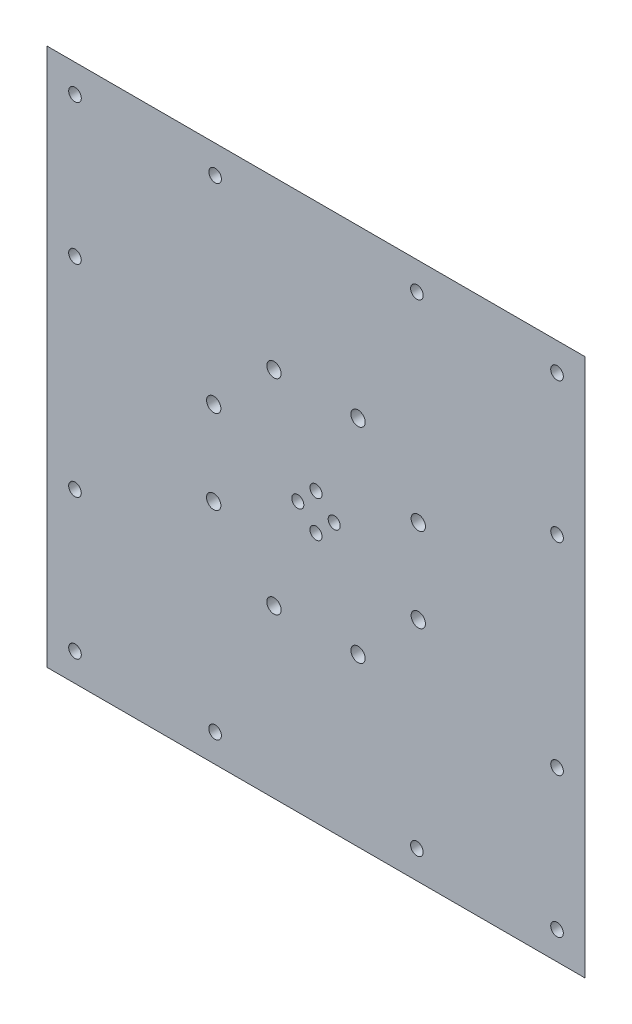
SolidWorks part; units mm, degrees
material "6061 합금"
ref_plane "정면" through (0, 0, 0) normal (0, 0, 1) x (1, 0, 0)
ref_plane "윗면" through (0, 0, 0) normal (0, 1, 0) x (1, 0, 0)
ref_plane "우측면" through (0, 0, 0) normal (1, 0, 0) x (0, 0, -1)
sketch "스케치1" plane through (0, 0, 0) normal (0, 0, 1) x (1, 0, 0)
  line L1 (-100, 100) -> (100, 100)
  line L2 (-100, 100) -> (-100, -100)
  line L3 (-100, -100) -> (100, -100)
  line L4 (100, 100) -> (100, -100)
  line L5 (-100, 100) -> (100, -100) construction
  line L6 (-100, -100) -> (100, 100) construction
  point P0 (0, 0)
  dimension "D1" = 200
  dimension "D2" = 200
extrude "보스-돌출1" add sketch "스케치1" along normal blind 3 contours L1 L4 L3 L2
sketch "스케치5" plane through (0, 0, 3) normal (0, 0, 1) x (1, 0, 0)
  line L1 (-100, 100) -> (100, 100)
  line L2 (-100, 100) -> (-100, -100)
  line L3 (-100, -100) -> (100, -100)
  line L4 (100, 100) -> (100, -100)
extrude "보스-돌출2" add sketch "스케치5" along normal blind 3
sketch "스케치2" plane through (0, 0, 0) normal (0, 0, 1) x (1, 0, 0)
  line L5 (-100, 100) -> (-100, -100) construction
  circle A0 centre (-36.5, 15) radius 2.55
  circle A2 centre (-36.5, -15) radius 2.55
  circle A4 centre (-6.5, 0) radius 2.15
  circle A5 centre (15, 36.5) radius 2.55
  circle A7 centre (-15, 36.5) radius 2.55
  circle A9 centre (0, 6.5) radius 2.15
  circle A10 centre (36.5, -15) radius 2.55
  circle A12 centre (36.5, 15) radius 2.55
  circle A14 centre (6.5, 0) radius 2.15
  circle A15 centre (-15, -36.5) radius 2.55
  circle A17 centre (15, -36.5) radius 2.55
  circle A19 centre (0, -6.5) radius 2.15
  point P2 (-36.5, -15.1647)
  point P46 (0, 0)
  dimension "D1" = 5.1
  dimension "D2" = 93.5
  dimension "D3" = 5.1
  dimension "D4" = 15
  dimension "D5" = 4.3
  dimension "D11" = 30
  dimension "D13" = 30
  dimension "D7" = 0
  dimension "D9" = 30
  dimension "D16" = 4
extrude "컷-돌출1" cut sketch "스케치2" along normal blind 10
chamfer "모따기1" distance 10 angle 45 4 edges at (0, 100, 0) (-100, 0, 0) (0, -100, 0) (100, 0, 0)
sketch "스케치6" plane through (0, 0, 0) normal (0, 0, -1) x (-1, 0, 0)
  line L1 (-96, 96) -> (-86, 96)
  line L2 (-96, 96) -> (-96, 86)
  line L3 (-96, 86) -> (-86, 86)
  line L4 (-86, 96) -> (-86, 86)
  line L5 (-96, -96) -> (-86, -96)
  line L6 (-96, -96) -> (-96, -86)
  line L7 (-96, -86) -> (-86, -86)
  line L8 (-86, -96) -> (-86, -86)
  line L9 (96, -96) -> (86, -96)
  line L10 (96, -96) -> (96, -86)
  line L11 (96, -86) -> (86, -86)
  line L12 (86, -96) -> (86, -86)
  line L13 (96, 96) -> (86, 96)
  line L14 (96, 96) -> (96, 86)
  line L15 (96, 86) -> (86, 86)
  line L16 (86, 96) -> (86, 86)
  dimension "D1" = 10
  dimension "D2" = 10
  dimension "D3" = 10
  dimension "D4" = 10
  dimension "D5" = 10
  dimension "D6" = 10
  dimension "D7" = 10
  dimension "D8" = 10
extrude "컷-돌출2" [suppressed] cut sketch "스케치6" against normal blind 4
hole_wizard "M4 여유 구멍1" positions "스케치3" profile "스케치4" hole size "M4" standard "KS"
sketch "스케치3" plane through (0, 0, 6) normal (0, 0, 1) x (1, 0, 0)
  line L10 (-96, -96) -> (96, -96) construction
  line L11 (96, -96) -> (96, 96) construction
  line L12 (-96, 96) -> (-96, -96) construction
  line L13 (96, 96) -> (-96, 96) construction
  point P0 (-86, -86)
  point P2 (-86, 86)
  point P4 (86, 86)
  point P6 (86, -86)
  point P47 (-86, -36)
  point P49 (-36, -86)
  point P51 (36, -86)
  point P53 (86, -36)
  point P55 (86, 36)
  point P57 (-36, 86)
  point P59 (36, 86)
  point P61 (-86, 36)
  point P71 (0, 0)
  point P72 (0, 0)
  dimension "D1" = 10
  dimension "D2" = 10
  dimension "D3" = 60
  dimension "D4" = 60
  dimension "D5" = 10
  dimension "D6" = 60
  dimension "D7" = 60
  dimension "D8" = 10
  dimension "D9" = 60
  dimension "D10" = 60
  dimension "D11" = 60
  dimension "D12" = 60
sketch "스케치4" plane through (-86, -86, 6) normal (1, 0, 0) x (0, -1, 0)
  line L0 (0, 0) -> (0, 7.3519)
  line L1 (0, 7.3519) -> (2.25, 6)
  line L2 (2.25, 6) -> (2.25, 0)
  line L5 (2.25, 0) -> (0, 0)
  line L10 (0, 7.3519) -> (-2.25, 6) construction
  line L11 (0, -6.35) -> (0, 107.95) construction
  dimension "구멍 지름" = 4.5
  dimension "구멍 깊이" = 6
  dimension "드릴 각도" = 118
